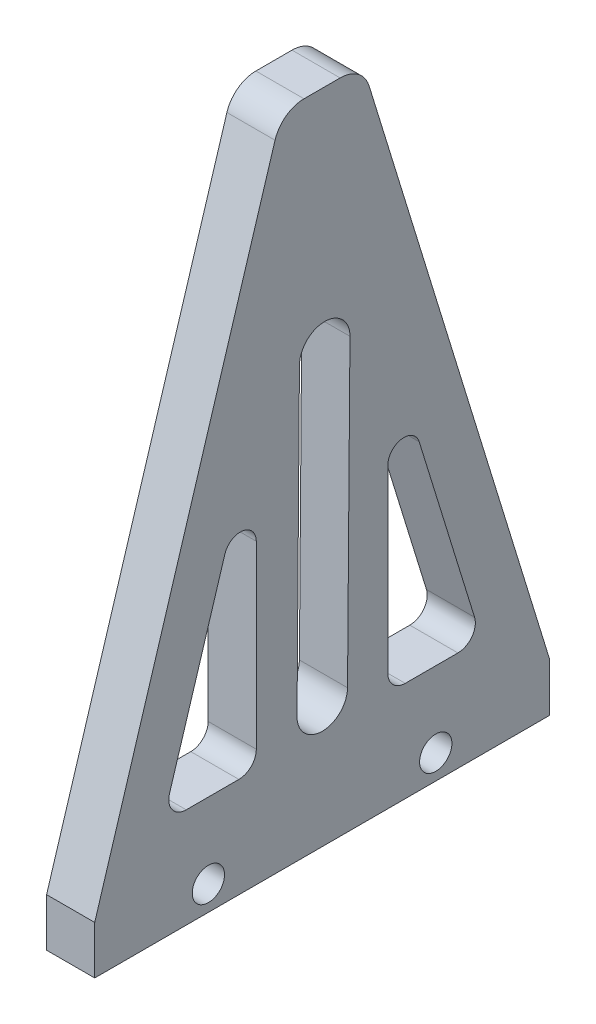
SolidWorks part; units mm, degrees
material "6061-T6 (SS)"
ref_plane "Front Plane" through (0, 0, 0) normal (0, 0, 1) x (1, 0, 0)
ref_plane "Top Plane" through (0, 0, 0) normal (0, 1, 0) x (1, 0, 0)
ref_plane "Right Plane" through (0, 0, 0) normal (1, 0, 0) x (0, 0, -1)
sketch "Sketch1" plane through (0, 0, 0) normal (1, 0, 0) x (0, 0, -1)
  line L0 (-22.5, 0) -> (22.5, 0)
  line L1 (-22.5, 0) -> (-22.5, 4.763)
  line L2 (22.5, 0) -> (22.5, 4.873)
  line L3 (0, 0) -> (0, 89.8135) construction
  line L4 (-4.6556, 62.8805) -> (-22.5, 4.763)
  line L5 (22.5, 4.873) -> (4.6552, 62.8821)
  line L6 (-1.7878, 65) -> (1.7878, 65)
  line L10 (6.5079, 11.613) -> (6.5079, 29.4345)
  line L11 (-9.6125, 29.9022) -> (-15.0943, 12.1213)
  line L12 (-13.4456, 9.8878) -> (-8.2332, 9.8878)
  line L13 (-6.5079, 11.613) -> (-6.5079, 29.4345)
  line L14 (13.4456, 9.8878) -> (8.2332, 9.8878)
  line L15 (9.6125, 29.9022) -> (15.0943, 12.1213)
  arc A2 (-6.5079, 29.4345) -> (-9.6125, 29.9022) centre (-8.0954, 29.4345) ccw
  arc A3 (-8.2332, 9.8878) -> (-6.5079, 11.613) centre (-8.2332, 11.613) ccw
  arc A4 (1.7878, 65) -> (4.6552, 62.8821) centre (1.7878, 62) cw
  arc A5 (-4.6556, 62.8805) -> (-1.7878, 65) centre (-1.7878, 62) cw
  arc A6 (-13.4456, 9.8878) -> (-15.0943, 12.1213) centre (-13.4456, 11.613) cw
  arc A7 (13.4456, 9.8878) -> (15.0943, 12.1213) centre (13.4456, 11.613) ccw
  arc A8 (8.2332, 9.8878) -> (6.5079, 11.613) centre (8.2332, 11.613) cw
  arc A9 (6.5079, 29.4345) -> (9.6125, 29.9022) centre (8.0954, 29.4345) cw
  point P9 (0, 65)
  point P11 (0, 12)
  point P12 (0, 47)
  point P20 (-22.5, 2.3815)
  point P21 (22.5, 2.4365)
  point P22 (-6.5079, 39.9722)
  point P31 (-6.5079, 9.8878)
  point P33 (-6.5079, 9.8878)
  point P34 (-15.7828, 9.8878)
  point P35 (-6.5079, 39.9722)
  point P39 (-15.7828, 9.8878)
  point P49 (15.7828, 9.8878)
  point P50 (6.5079, 39.9722)
  point P51 (6.5079, 9.8878)
  dimension "D1" = 3
  dimension "D2" = 1.5875
  dimension "D3" = 1.7252
  dimension "D4" = 4.763
  dimension "D5" = 45
  dimension "D6" = 65
  dimension "D7" = 35
  dimension "D8" = 6.5079
extrude "Boss-Extrude1" add sketch "Sketch1" along normal mid plane 4.763
hole_wizard "M3 Clearance Hole1" positions "Sketch3" profile "Sketch2" hole size "M3" standard "ANSI Metric" end condition through all
sketch "Sketch3" plane through (2.3815, 0, 0) normal (1, 0, 0) x (0, 0, -1)
  line L4 (22.5, 0) -> (22.5, 4.873) construction
  line L5 (-22.5, 2.3815) -> (22.5, 2.4365) construction
  point P0 (11.25, 2.4365)
  point P2 (-11.2501, 2.4365)
sketch "Sketch2" plane through (2.3815, 2.4365, -11.25) normal (0, 1, 0) x (0, 0, -1)
  line L0 (0, 0) -> (0, 4.763)
  line L1 (0, 4.763) -> (1.6, 4.763)
  line L2 (1.6, 4.763) -> (1.6, 0)
  line L5 (1.6, 0) -> (0, 0)
  line L11 (0, -6.35) -> (0, 107.95) construction
  dimension "Thru Hole Dia." = 3.2
  dimension "Thru Hole Depth" = 4.763
hole_wizard "Ø1.0mm Dowel Slot1" positions "Sketch5" profile "Sketch4" size "Ø1.0" standard "ANSI Metric" slot yes
sketch "Sketch5" plane through (2.3815, 0, 0) normal (1, 0, 0) x (0, 0, -1)
  line L2 (-13.4456, 9.8878) -> (13.4456, 9.8878) construction
  line L8 (0, 9.8878) -> (0.2817, 44.8867) construction
  point P0 (0.1408, 27.3872)
  dimension "D1" = 35
sketch "Sketch4" plane through (2.3815, 27.3872, -0.1408) normal (0, 1, 0) x (0, 0, -1)
  line L0 (0, 0) -> (0, 11.5022)
  line L1 (0, 11.5022) -> (2.5, 10)
  line L2 (2.5, 10) -> (2.5, 0)
  line L5 (2.5, 0) -> (0, 0)
  line L10 (0, 11.5022) -> (-2.5, 10) construction
  line L11 (0, -6.35) -> (0, 107.95) construction
  dimension "Hole Dia." = 5
  dimension "Hole Depth" = 10
  dimension "Drill Angle" = 118
